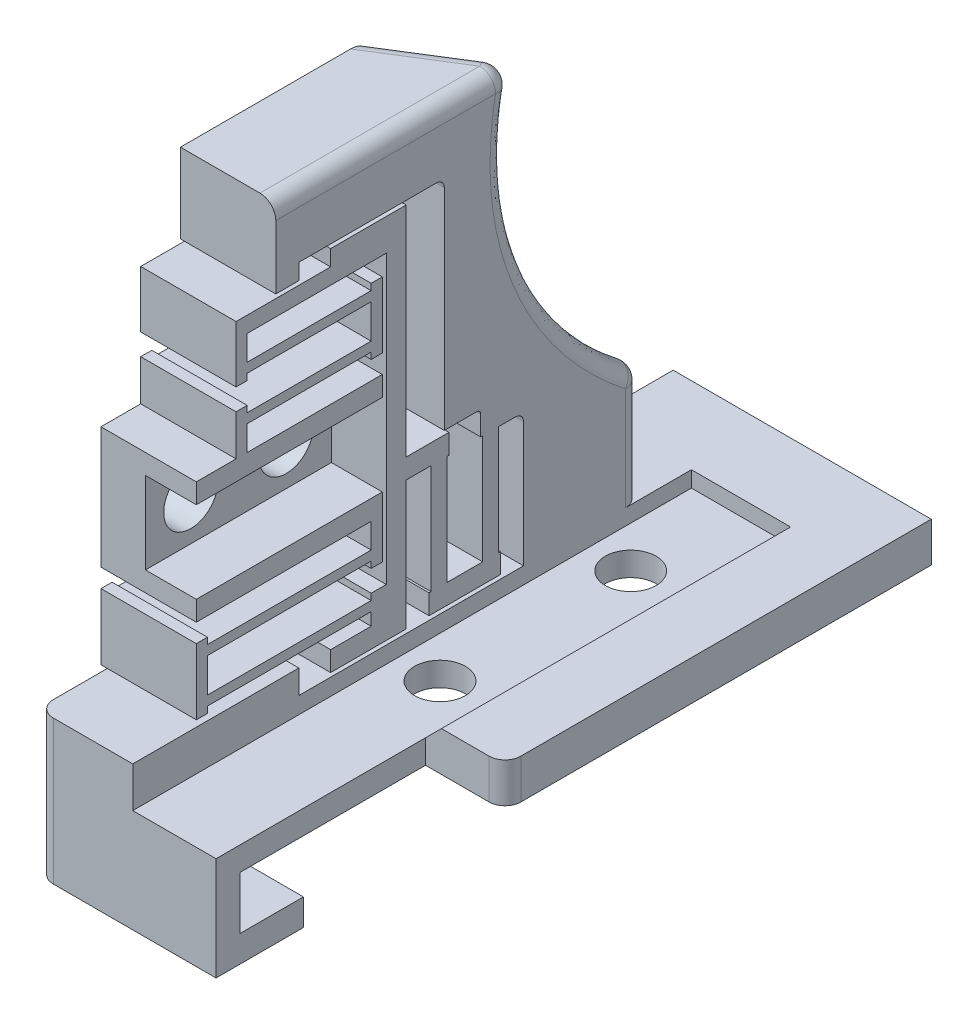
SolidWorks part; units mm, degrees
other "Markup1"
sketch "Sketch8" plane through (10.5, 0, 3) normal (0.7095, 0.0467, 0.7031) x (0.7044, -0.0184, -0.7096)
ref_plane "Front Plane" through (0, 0, 0) normal (0, 0, 1) x (1, 0, 0)
ref_plane "Top Plane" through (0, 0, 0) normal (0, 1, 0) x (1, 0, 0)
ref_plane "Right Plane" through (0, 0, 0) normal (1, 0, 0) x (0, 0, -1)
sketch "Sketch1" plane through (0, 0, 0) normal (1, 0, 0) x (0, 0, -1)
  line L0 (-1.8, -12.735) -> (6.7, -12.735)
  line L1 (6.7, -12.735) -> (6.7, -22.9528)
  line L2 (-5, -12.735) -> (-5, -20.385)
  line L3 (-5, -20.385) -> (6, -20.385)
  line L57 (-4.3, -22.5522) -> (-4.3, -24.7028)
  line L58 (-4.3, -24.7028) -> (6, -24.7028)
  line L60 (6, -20.385) -> (6, -21.9522)
  line L62 (-5, -21.5517) -> (-5, -25.7033)
  line L64 (6.95, -6.25) -> (6.95, -24.3022)
  line L65 (-1.8, -11.1678) -> (6, -11.1678)
  line L66 (6, -10.5678) -> (6, -8.4172)
  line L68 (-2.5, -8.8178) -> (-2.5, -5.25)
  line L69 (-1.8, -12.735) -> (-1.8, -11.1678)
  line L71 (6.7, -11.5683) -> (6.7, -7.4167)
  line L73 (-1.8, -7.8172) -> (-1.8, -6.25)
  line L74 (-1.8, -6.25) -> (6.95, -6.25)
  line L75 (-2.5, -5.25) -> (3.45, -5.25)
  line L79 (6, -11.1678) -> (6, -11.5683)
  line L80 (6, -11.5683) -> (6.7, -11.5683)
  line L85 (6, -10.5678) -> (-1.8, -10.5678)
  line L86 (-1.8, -10.5678) -> (-1.8, -10.1672)
  line L87 (-1.8, -10.1672) -> (-2.5, -10.1672)
  line L90 (6, -8.4172) -> (-1.8, -8.4172)
  line L93 (-1.8, -7.8172) -> (6, -7.8172)
  line L98 (6, -7.8172) -> (6, -7.4167)
  line L99 (6, -7.4167) -> (6.7, -7.4167)
  line L102 (6, -21.9522) -> (-4.3, -21.9522)
  line L103 (-4.3, -21.9522) -> (-4.3, -21.5517)
  line L104 (-4.3, -21.5517) -> (-5, -21.5517)
  line L105 (6.7, -22.9528) -> (6, -22.9528)
  line L106 (6, -22.9528) -> (6, -22.5522)
  line L111 (6, -22.5522) -> (-4.3, -22.5522)
  line L115 (6, -24.7028) -> (6, -24.3022)
  line L116 (6, -24.3022) -> (6.95, -24.3022)
  line L117 (-5, -25.7033) -> (-4.3, -25.7033)
  line L118 (-4.3, -25.7033) -> (-4.3, -25.3028)
  line L119 (-4.3, -25.3028) -> (6, -25.3028)
  line L124 (6, -25.3028) -> (6, -26.1033)
  line L126 (6, -26.1033) -> (3.45, -26.1033)
  line L127 (3.45, -26.1033) -> (3.45, -27.3533)
  line L128 (3.45, -27.3533) -> (8.2, -27.3533)
  line L130 (13.0172, -26.1033) -> (10.7672, -26.1033)
  line L131 (10.7672, -26.1033) -> (10.7672, -19.235)
  line L136 (10.7672, -19.235) -> (10.8922, -19.235)
  line L141 (13.0172, -19.235) -> (13.0172, -26.1033)
  line L145 (9.7672, -26.1033) -> (9.6422, -26.1033)
  line L146 (9.7672, -26.1033) -> (9.7672, -19.235)
  line L150 (9.7672, -19.235) -> (8.2, -19.235)
  line L153 (8.2, -17.985) -> (10.8922, -17.985)
  line L155 (15.0844, -19.235) -> (14.0172, -19.235)
  line L160 (14.0172, -19.235) -> (14.0172, -26.1033)
  line L168 (15.5844, -27.6033) -> (15.5844, -19.735)
  line L179 (15.5844, -27.6033) -> (1.45, -27.6033)
  line L180 (1.45, -27.6033) -> (1.45, -26.1033)
  line L181 (1.45, -26.1033) -> (-9, -26.1033)
  line L184 (-9, -30.15) -> (23, -30.15)
  line L187 (23, 0) -> (0, 0)
  line L189 (8.2, -27.3533) -> (8.2, -19.235)
  line L190 (1.45, -5) -> (0, -5)
  line L191 (0, -5) -> (0, 0)
  line L192 (14.1422, -26.1033) -> (14.0172, -26.1033)
  line L193 (12.6422, -17.735) -> (10.6, -17.735)
  line L194 (10.6, -17.735) -> (10.6, -4.5)
  line L198 (9.6422, -26.1033) -> (9.6422, -27.3533)
  line L199 (14.1422, -26.1033) -> (14.1422, -27.3533)
  line L200 (14.1422, -27.3533) -> (9.6422, -27.3533)
  line L201 (8.2, -17.985) -> (8.2, -4.25)
  line L203 (12.8922, -19.235) -> (12.8922, -17.985)
  line L204 (10.8922, -19.235) -> (10.8922, -17.985)
  line L205 (12.8922, -19.235) -> (13.0172, -19.235)
  line L212 (-9, -30.15) -> (-9, -26.1033)
  line L214 (-2.5, -12.735) -> (-5, -12.735)
  line L215 (-2.5, -12.735) -> (-2.5, -10.1672)
  line L216 (23, 0) -> (23, -30.15)
  line L217 (1.45, -5) -> (1.45, -4)
  line L218 (1.45, -4) -> (10.1, -4)
  line L219 (3.45, -5.25) -> (3.45, -4.25)
  line L220 (3.45, -4.25) -> (8.2, -4.25)
  line L221 (14.0172, -19.235) -> (15.5844, -19.235) construction
  line L222 (-2.5, -8.8178) -> (-1.8, -8.8178)
  line L223 (-1.8, -8.8178) -> (-1.8, -8.4172)
  arc A4 (15.0844, -19.235) -> (15.5844, -19.735) centre (15.0844, -19.735) cw
  arc A5 (12.8922, -17.985) -> (12.6422, -17.735) centre (12.6422, -17.985) ccw
  arc A6 (10.1, -4) -> (10.6, -4.5) centre (10.1, -4.5) cw
  circle A7 centre (3.85, -16.56) radius 1.7
  circle A8 centre (-2.15, -16.56) radius 1.7
  circle A9 centre (-2.15, -16.56) radius 2.85 construction
  circle A10 centre (3.85, -16.56) radius 2.85 construction
  point P120 (10.6, -5)
  point P140 (15.5844, -19.235)
  point P144 (12.8922, -17.735)
  point P151 (-5, -16.56)
  dimension "D61" = 0.5
  dimension "D62" = 0.25
  dimension "D66" = 0.5
  dimension "D67" = 3.4
  dimension "D68" = 5.7
  dimension "D6" = 0.6
  dimension "D9" = 0.6
  dimension "D10" = 1.1667
  dimension "D17" = 0.6
  dimension "D21" = 0.6
  dimension "D23" = 1
  dimension "D24" = 0.25
  dimension "D37" = 0.7
  dimension "D40" = 0.25
  dimension "D44" = 1
  dimension "D12" = 7.65
  dimension "D20" = 1.25
  dimension "D26" = 1.25
  dimension "D28" = 0.25
  dimension "D33" = 1.25
  dimension "D49" = 2.4
  dimension "D50" = 0.25
  dimension "D31" = 5
  dimension "D54" = 5
  dimension "D55" = 0.7
  dimension "D65" = 2.5
  dimension "D64" = 2.5
  dimension "D29" = 2
  dimension "D52" = 0.25
  dimension "D56" = 1
  dimension "D69" = 6
  dimension "D39" = 4
  dimension "D51" = 32
  dimension "D22" = 1.1667
  dimension "D53" = 2
  dimension "D7" = 0.4
  dimension "D8" = 1.45
  dimension "D11" = 1
  dimension "D13" = 4.5
  dimension "D14" = 2
  dimension "D15" = 30.15
  dimension "D16" = 0.7
  dimension "D25" = 1.25
  dimension "D18" = 13.59
  dimension "D19" = 1.75
extrude "Boss-Extrude1" add sketch "Sketch1" along normal blind 6
sketch "Sketch2" plane through (0, 0, 5) normal (0, 0, 1) x (1, 0, 0)
  line L0 (6, -12.735) -> (6, -20.385) construction
  line L1 (6, -19.135) -> (2.8, -19.135)
  line L2 (6, -19.135) -> (6, -13.985)
  line L3 (6, -13.985) -> (2.8, -13.985)
  line L4 (2.8, -19.135) -> (2.8, -13.985)
  line L5 (6, -12.735) -> (6, -20.385) construction
  dimension "D1" = 3.2
  dimension "D2" = 1.25
  dimension "D3" = 1.25
extrude "Cut-Extrude4" cut sketch "Sketch2" against normal up to next
sketch "Sketch3" plane through (0, -30.15, 0) normal (0, -1, 0) x (1, 0, 0)
  line L0 (11.24, -4.18) -> (16.24, -4.18)
  line L1 (0, -31) -> (16.24, -31)
  line L2 (0, -31) -> (0, 9)
  line L4 (11.24, -4.18) -> (11.24, 9)
  line L5 (6, 9) -> (6, -23) construction
  line L7 (16.24, -31) -> (16.24, -4.18)
  line L8 (0, 9) -> (0, -23) construction
  line L9 (11.24, 9) -> (0, 9)
  circle A0 centre (8.6, -7.73) radius 1.6
  circle A1 centre (8.6, -19.73) radius 1.6
  dimension "D3" = 3.2
  dimension "D1" = 13.18
  dimension "D2" = 2.6
  dimension "D4" = 12
  dimension "D5" = 5
  dimension "D6" = 40
  dimension "D7" = 16.73
  dimension "D8" = 11.24
sketch "Sketch7" plane through (0, 0, 0) normal (-1, 0, 0) x (0, 0, 1)
  line L0 (2.5, -12.735) -> (5, -12.735) construction
  line L2 (-6.7, -12.735) -> (-6.7, -22.9528) construction
  circle A0 centre (2.15, -16.61) radius 1.7
  circle A1 centre (-3.85, -16.61) radius 1.7
  circle A2 centre (2.15, -16.61) radius 2.85 construction
  circle A3 centre (-3.85, -16.61) radius 2.85 construction
  dimension "D1" = 3.4
  dimension "D2" = 3.875
  dimension "D5" = 5.7
  dimension "D3" = 6
extrude "Cut-Extrude3" cut sketch "Sketch7" against normal up to next
extrude "Boss-Extrude2" add sketch "Sketch3" against normal blind 2.5
sketch "Sketch12" plane through (0, 0, 9) normal (0, 0, 1) x (1, 0, 0)
  line L0 (6, -26.1033) -> (6, -27.65) construction
  line L1 (11.24, -27.65) -> (6, -27.65)
  line L2 (11.24, -27.65) -> (11.24, -28.65)
  line L3 (11.24, -28.65) -> (6, -28.65)
  line L4 (6, -27.65) -> (6, -28.65)
  line L5 (11.24, -27.65) -> (6, -27.65) construction
  dimension "D1" = 1
  dimension "D2" = 5.24
extrude "Cut-Extrude6" cut sketch "Sketch12" against normal blind 35.15
sketch "Sketch14" plane through (0, 0, 0) normal (-1, 0, 0) x (0, 0, 1)
  line L1 (9, -30.15) -> (3.5, -30.15)
  line L2 (9, -30.15) -> (9, -35.15)
  line L3 (9, -35.15) -> (3.5, -35.15)
  line L4 (3.5, -30.15) -> (3.5, -35.15)
  line L6 (9, -26.1033) -> (9, -30.15) construction
  dimension "D2" = 5
  dimension "D3" = 5.5
extrude "Boss-Extrude4" add sketch "Sketch14" against normal blind 11.24
sketch "Sketch15" plane through (11.24, 0, 0) normal (1, 0, 0) x (0, 0, -1)
  line L1 (-3.5, -30.15) -> (-7.5, -30.15)
  line L2 (-3.5, -30.15) -> (-3.5, -33.48)
  line L3 (-3.5, -33.48) -> (-7.5, -33.48)
  line L4 (-7.5, -30.15) -> (-7.5, -33.48)
  dimension "D1" = 4
  dimension "D2" = 3.33
extrude "Cut-Extrude7" cut sketch "Sketch15" against normal blind 10.25
ref_plane "Plane2" through (0, 0, 7.1) normal (0, 0, 1) x (1, 0, 0)
ref_axis "Axis1" through (11.24, 27.1504, 7.1) along (0, -1, 0)
mirror "Mirror1" [suppressed] of bodies 111
delete or keep bodies "Body-Delete/Keep 1" [suppressed] type delete bodies bodies 111
ref_plane "Plane1" through (4.8929, 0, -3.0574) normal (-0.848, 0, 0.5299) x (0, -1, 0)
sketch "Sketch10" plane through (4.8929, 0, -3.0574) normal (-0.848, 0, 0.5299) x (0, -1, 0)
  line L0 (30.15, 13.5887) -> (30.15, 7.6324) construction
  line L1 (30.15, 2.9682) -> (30.15, -26.2895) construction
  line L2 (30.15, 12.3167) -> (30.15, -33.4435) construction
  circle A0 centre (4.65, -31.2799) radius 21.5
  dimension "D2" = 43
  dimension "D1" = 43.5966
  dimension "D3" = 25.5
extrude "Cut-Extrude5" cut sketch "Sketch10" against normal blind 25
fillet "Fillet1" radius 1 9 edges at (3.1138, -21.4436, -23) (3, 0, -14.0069) (6, -23.8736, -23) (6, -10.8352, -16.3532) (6, 0, -7.9408) (16.24, -28.9, -4.18) (0.99, -31.815, 7.5) (0, -30.6267, 9) (0.495, -30.15, 3.5)
chamfer "Chamfer1" distance 1 angle 45 1 edges at (11.24, -27.65, -15.165)
mirror "Mirror2" [suppressed] of bodies 113
delete or keep bodies "Body-Delete/Keep 2" [suppressed] type delete bodies bodies 113
equation "\"VerticalFlexureWidth\"= 0.6"
equation "\"VerticalFlexureGap\"= 1"
equation "\"VerticalDoubleFlexureWidth\"= 2 * \"VerticalFlexureWidth\" + \"VerticalFlexureGap\""
equation "\"HorizontalFlexureLength\"= 7"
equation "\"FlexureJointWidth\"=1.25"
equation "\"HeadHeight\"= 7.5"
equation "\"VerticalFlexureLength\"= 18"
equation "\"MinGap\"=0.25"
equation "\"BaseplateHeight+Tolerance\"= 3.33"
equation "\"HeadWidth\"= 13"
equation "\"HorizontalFlexureWidth\"= 1"
equation "\"HorizontalFlexureGap\"= 1"
equation "\"HorizontalDoubleFlexureWidth\"= 2 * \"HorizontalFlexureWidth\" + \"HorizontalFlexureGap\""
equation "\"FlexureWidth\"=0.85"
equation "\"FlexureWideWidth\"= 0.8"
equation "\"FlexureGap\"=1.75"
equation "\"TwinFlexureWidth\"= \"FlexureGap\" + 2 * \"FlexureWideWidth\""
equation "\"FlexureNeckWidth\"= ( \"FlexureWideWidth\" - \"FlexureWidth\" ) / 2"
equation "\"D6@Sketch1\"=\"VerticalFlexureWidth\""
equation "\"D9@Sketch1\"=\"VerticalFlexureWidth\""
equation "\"D21@Sketch1\"=\"VerticalFlexureWidth\""
equation "\"FlexureLength\"= 2"
equation "\"MainSupport\"=1.5"
equation "\"D24@Sketch1\"=\"MinGap\""
equation "\"D37@Sketch1\"=\"FlexureJointWidthVertical\""
equation "\"D40@Sketch1\"=\"MinGap\""
equation "\"D44@Sketch1\"=\"HorizontalFlexureWidth\""
equation "\"D20@Sketch1\"=\"MainSupport\"-0.25"
equation "\"D26@Sketch1\"=\"FlexureJointWidth\""
equation "\"D28@Sketch1\"=\"MinGap\""
equation "\"D33@Sketch1\"=\"FlexureJointWidth\""
equation "\"FlexureGapEdge\"= \"FlexureGap\" * ( 2 / 3 )"
equation "\"D55@Sketch1\"=\"FlexureJointWidthVertical\""
equation "\"FlexurePlateConnectionHeigh\"= 5.15 + 2.5"
equation "\"D12@Sketch1\"=\"FlexurePlateConnectionHeigh\""
equation "\"D52@Sketch1\"=\"MinGap\""
equation "\"D17@Sketch1\"=\"VerticalFlexureWidth\""
equation "\"D11@Sketch1\"=\"HorizontalFlexureWidth\""
equation "\"D16@Sketch1\"=\"FlexureJointWidthVertical\""
equation "\"D25@Sketch1\"=\"FlexureJointWidth\""
equation "\"FlexureJointWidthVertical\"= 0.7"
